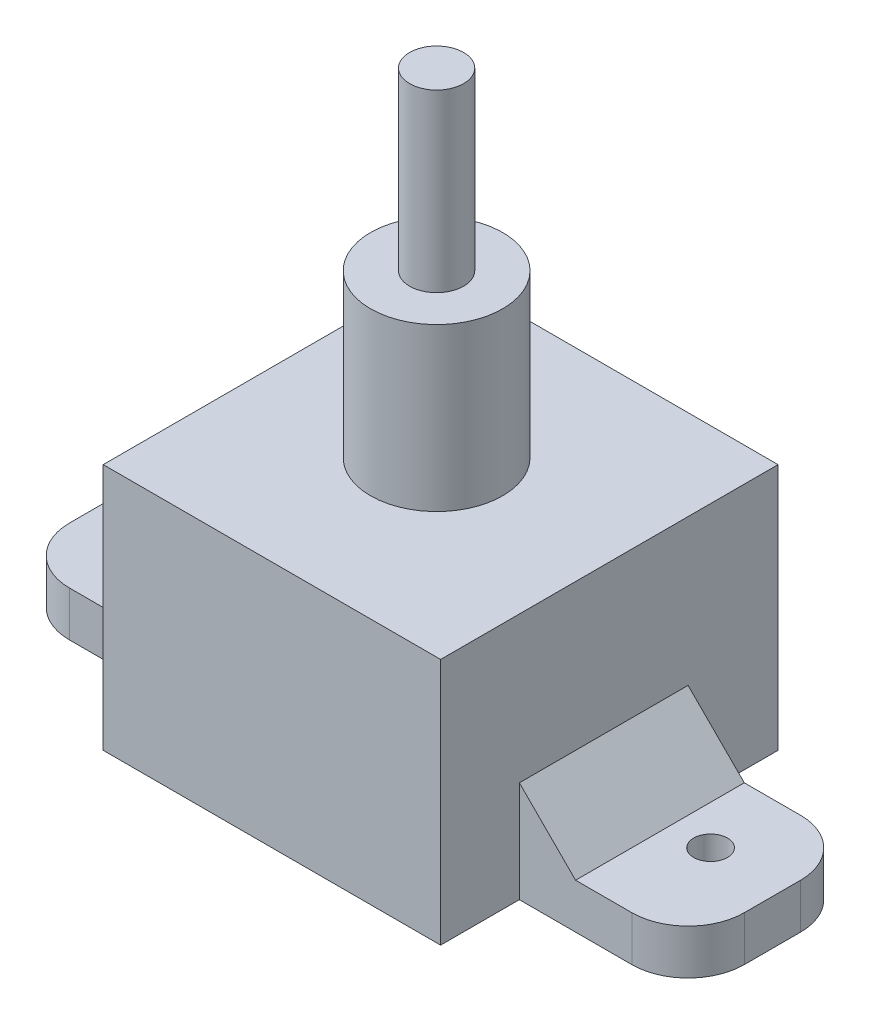
SolidWorks part; units mm, degrees
ref_plane "Спереди" through (0, 0, 0) normal (0, 0, 1) x (1, 0, 0)
ref_plane "Сверху" through (0, 0, 0) normal (0, 1, 0) x (1, 0, 0)
ref_plane "Справа" through (0, 0, 0) normal (1, 0, 0) x (0, 0, -1)
other "Configuration Table"
sketch "Эскиз1" plane through (0, 0, 0) normal (0, 1, 0) x (1, 0, 0)
  line L1 (-14.2865, 14.6433) -> (15.7135, 14.6433)
  line L2 (-14.2865, 14.6433) -> (-14.2865, -15.3567)
  line L3 (-14.2865, -15.3567) -> (15.7135, -15.3567)
  line L4 (15.7135, 14.6433) -> (15.7135, -15.3567)
  dimension "D1" = 30
  dimension "D2" = 30
extrude "высота " add sketch "Эскиз1" along normal blind 22
sketch "Эскиз2" plane through (0, 22, 0) normal (0, 1, 0) x (1, 0, 0)
  circle A0 centre (0, 0) radius 5.875
  dimension "D1" = 11.75
sketch "Эскиз3" plane through (0, 0, 0) normal (0, 0, 1) x (1, 0, 0)
  line L0 (0, 49.97) -> (0, -1.7648) construction
extrude "Бобышка-Вытянуть2" add sketch "Эскиз2" along normal blind 14.4 contours A0
sketch "Эскиз4" plane through (0, 36.4, 0) normal (0, 1, 0) x (1, 0, 0)
  circle A0 centre (0, 0) radius 2.4
  dimension "D1" = 4.8
extrude "Бобышка-Вытянуть3" add sketch "Эскиз4" along normal blind 15.6
sketch "Эскиз5" plane through (0, 0, 0) normal (0, -1, 0) x (1, 0, 0)
  line L0 (15.7135, 15.3567) -> (15.7135, -14.6433) construction
  line L1 (15.7135, 8.3567) -> (25.7135, 8.3567)
  line L2 (15.7135, 8.3567) -> (15.7135, -6.6433)
  line L3 (15.7135, -6.6433) -> (25.7135, -6.6433)
  line L4 (30.7135, 3.3567) -> (30.7135, -1.6433)
  line L5 (15.7135, -14.6433) -> (-14.2865, -14.6433) construction
  line L6 (0, 0) -> (0, -14.6433) construction
  line L12 (-14.2865, -14.6433) -> (-14.2865, 15.3567) construction
  line L13 (-14.2865, 8.3567) -> (-24.2865, 8.3567)
  line L14 (-14.2865, 8.3567) -> (-14.2865, -6.6433)
  line L15 (-14.2865, -6.6433) -> (-24.2865, -6.6433)
  line L16 (-29.2865, 3.3567) -> (-29.2865, -1.6433)
  arc A0 (-29.2865, 3.3567) -> (-24.2865, 8.3567) centre (-24.2865, 3.3567) cw
  arc A1 (-24.2865, -6.6433) -> (-29.2865, -1.6433) centre (-24.2865, -1.6433) cw
  arc A2 (30.7135, 3.3567) -> (25.7135, 8.3567) centre (25.7135, 3.3567) ccw
  arc A3 (30.7135, -1.6433) -> (25.7135, -6.6433) centre (25.7135, -1.6433) cw
  point P19 (-29.2865, 8.3567)
  point P22 (-29.2865, -6.6433)
  point P25 (30.7135, 8.3567)
  point P28 (30.7135, -6.6433)
  dimension "D7" = 5
  dimension "D8" = 5
  dimension "D9" = 5
  dimension "D10" = 5
  dimension "D1" = 15
  dimension "D2" = 15
  dimension "D3" = 8
  dimension "D4" = 15
  dimension "D5" = 15
  dimension "D6" = 8
extrude "Бобышка-Вытянуть4" add sketch "Эскиз5" against normal blind 4
sketch "Эскиз6" plane through (0, 4, 0) normal (0, 1, 0) x (1, 0, 0)
  line L0 (30.7135, 1.6433) -> (30.7135, -3.3567) construction
  line L1 (15.7135, 6.6433) -> (25.7135, 6.6433) construction
  line L2 (-24.2865, 6.6433) -> (-14.2865, 6.6433) construction
  line L3 (-29.2865, -3.3567) -> (-29.2865, 1.6433) construction
  circle A0 centre (24.2135, 0.1433) radius 1.5
  circle A1 centre (-22.7865, 0.1433) radius 1.5
  dimension "D1" = 3
  dimension "D4" = 3
  dimension "D2" = 6.5
  dimension "D3" = 6.5
  dimension "D5" = 6.5
  dimension "D6" = 6.5
extrude "Вырез-Вытянуть2" cut sketch "Эскиз6" against normal through all both and the other way through all contours A1 | A0
chamfer "Фаска2" distance 5 angle 45 1 edges at (15.7135, 4, 0.8567)
chamfer "Фаска3" distance 5 angle 45 1 edges at (-14.2865, 4, 0.8567)
